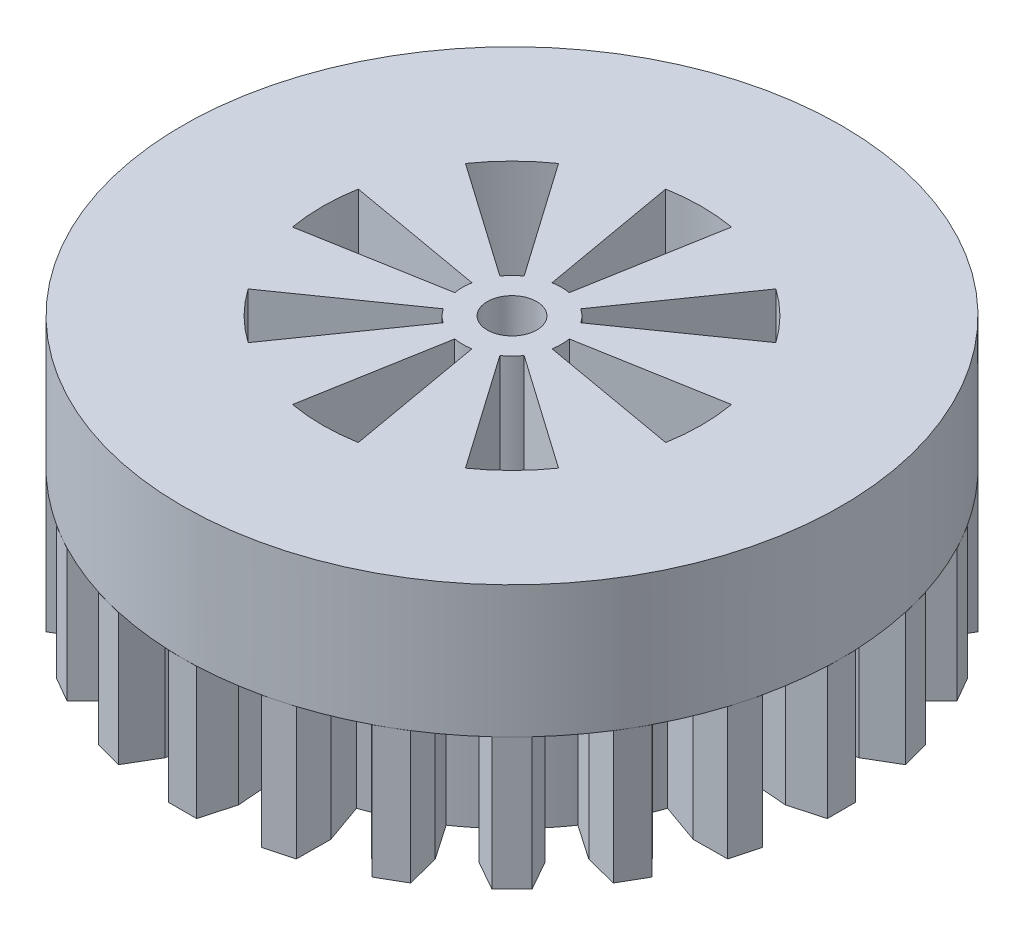
SolidWorks part; units mm, degrees
ref_plane "Front Plane" through (0, 0, 0) normal (0, 0, 1) x (1, 0, 0)
ref_plane "Top Plane" through (0, 0, 0) normal (0, 1, 0) x (1, 0, 0)
ref_plane "Right Plane" through (0, 0, 0) normal (1, 0, 0) x (0, 0, -1)
sketch "Sketch1" plane through (0, 0, 0) normal (0, 1, 0) x (1, 0, 0)
  circle A0 centre (0, 0) radius 15.5
  dimension "D1" = 31
extrude "Boss-Extrude1" add sketch "Sketch1" along normal blind 8
sketch "Sketch2" plane through (0, 8, 0) normal (0, 1, 0) x (1, 0, 0)
  line L0 (0, 0) -> (-20, 0)
  line L1 (-20, 1.57) -> (0, 0)
  line L2 (-20, -1.57) -> (0, 0)
  line L3 (-20, 1.57) -> (-20, -1.57)
  point P8 (-20, 0)
  circle M5 centre (0, 0) radius 15.5
  dimension "D1" = 20
  dimension "D6" = 3.14
extrude "Boss-Extrude2" add sketch "Sketch2" against normal blind 8 contours L0 L3 L2 M5 | L1 L3 L0 M5 | L1 L0 M5 | L2 L0 M5 region at (-10.3228, 8, 0.4045) region at (-10.3228, 8, -0.4045) region at (-17.8378, 8, 0.7011) region at (-17.8378, 8, -0.7011)
chamfer "Chamfer1" distance 2 angle 20 1 edges at (-20, 4, 1.57) first distance on face at (-17.7262, 4, 1.3915)
chamfer "Chamfer2" distance 2 angle 20 1 edges at (-20, 4, -1.57) first distance on face at (-17.7262, 4, -1.3915)
pattern_circular "CirPattern1" count 24 over 360 about axis through (0, 8, 0) along (0, 1, 0) of "Boss-Extrude2", "Chamfer1", "Chamfer2"
sketch "Sketch3" plane through (0, 8, 0) normal (0, 1, 0) x (1, 0, 0)
  circle A0 centre (0, 0) radius 20
  dimension "D1" = 40
extrude "Boss-Extrude3" add sketch "Sketch3" along normal blind 8
sketch "Sketch4" plane through (0, 0, 0) normal (0, -1, 0) x (1, 0, 0)
  circle A0 centre (0, 0) radius 3
  dimension "D1" = 6
extrude "Boss-Extrude4" add sketch "Sketch4" along normal blind 7
sketch "Sketch5" plane through (0, 0, 0) normal (0, -1, 0) x (1, 0, 0)
  line L0 (0, 0) -> (-18.5534, 0)
  line L1 (0, 0) -> (-11.3253, -1.997)
  line L2 (0, 0) -> (-11.3253, 1.997)
  line L3 (-11.3253, 1.997) -> (-11.3253, -1.997)
  arc A0 (-11.3253, -1.997) -> (-11.3253, 1.997) centre (0, 0) cw
  circle A1 centre (0, 0) radius 3
  dimension "D1" = 10
  dimension "D2" = 10
  dimension "D3" = 11.5
extrude "Cut-Extrude1" cut sketch "Sketch5" against normal through all contours L0 L3 L1 | L2 L3 L0 | A0 L0 L3 | A0 L3 L0 region at (-7.9652, 0, -0.7023) region at (-7.9652, 0, 0.7023) region at (-11.3952, 0, -0.7496) region at (-11.3952, 0, 0.7496)
pattern_circular "CirPattern2" count 8 over 360 about axis through (0, 16, 0) along (0, 1, 0) of "Cut-Extrude1"
sketch "Sketch6" plane through (0, -7, 0) normal (0, -1, 0) x (1, 0, 0)
  circle A0 centre (0, 0) radius 1.5
  dimension "D1" = 3
extrude "Cut-Extrude2" cut sketch "Sketch6" against normal through all
equation "\"D1@Sketch2\"=\"D1@Sketch1\"/2+4.5"
equation "\"D1@Sketch3\"=\"D1@Sketch1\"+4.5*2"
equation "\"D3@Sketch5\"=\"D1@Sketch1\"/2-4"
